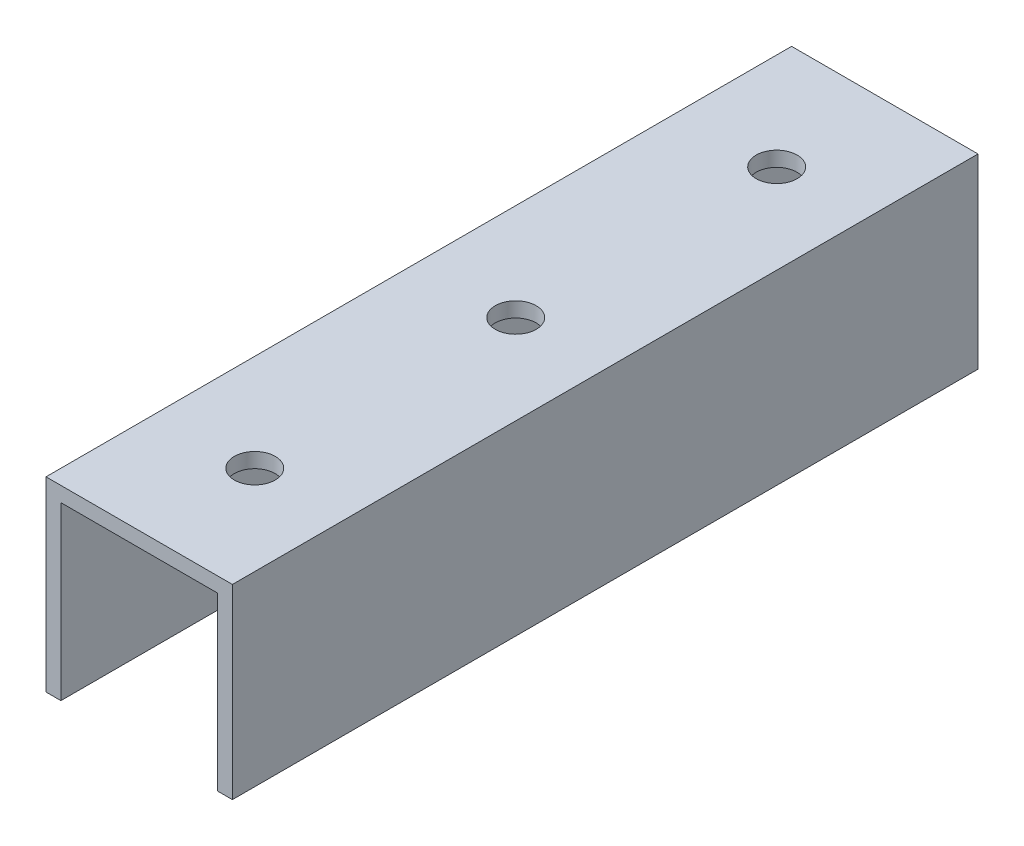
SolidWorks part; units mm, degrees
material "1060 Alloy"
ref_plane "Płaszczyzna przednia" through (0, 0, 0) normal (0, 0, 1) x (1, 0, 0)
ref_plane "Płaszczyzna górna" through (0, 0, 0) normal (0, 1, 0) x (1, 0, 0)
ref_plane "Płaszczyzna prawa" through (0, 0, 0) normal (1, 0, 0) x (0, 0, -1)
sketch "Szkic1" plane through (0, 0, 0) normal (0, 0, 1) x (1, 0, 0)
  line L0 (0, 0) -> (0, 25)
  line L1 (0, 25) -> (25, 25)
  line L2 (25, 25) -> (25, 0)
  line L3 (25, 0) -> (23, 0)
  line L4 (23, 0) -> (23, 23)
  line L5 (23, 23) -> (2, 23)
  line L6 (2, 23) -> (2, 0)
  line L7 (2, 0) -> (0, 0)
  dimension "D1" = 2
  dimension "D2" = 2
  dimension "D3" = 2
  dimension "D4" = 25
  dimension "D5" = 25
extrude "Dodanie-wyciągnięcie1" add sketch "Szkic1" along normal blind 100
hole_wizard "M5 Clearance Hole1" positions "Sketch1" profile "Sketch2" hole size "M5" standard "ISO" end condition through all
sketch "Sketch1" plane through (0, 25, 0) normal (0, 1, 0) x (1, 0, 0)
  line L0 (25, -100) -> (0, -100) construction
  line L1 (25, -100) -> (25, 0) construction
  point P0 (13, -50)
  point P2 (13, -15)
  point P4 (13, -85)
  dimension "D1" = 35
  dimension "D2" = 35
  dimension "D3" = 15
  dimension "D4" = 12
sketch "Sketch2" plane through (13, 25, 50) normal (1, 0, 0) x (0, 0, 1)
  line L0 (0, 0) -> (0, 25)
  line L1 (0, 25) -> (2.75, 25)
  line L2 (2.75, 25) -> (2.75, 0)
  line L5 (2.75, 0) -> (0, 0)
  line L11 (0, -6.35) -> (0, 107.95) construction
  dimension "Thru Hole Dia." = 5.5
  dimension "Thru Hole Depth" = 25
